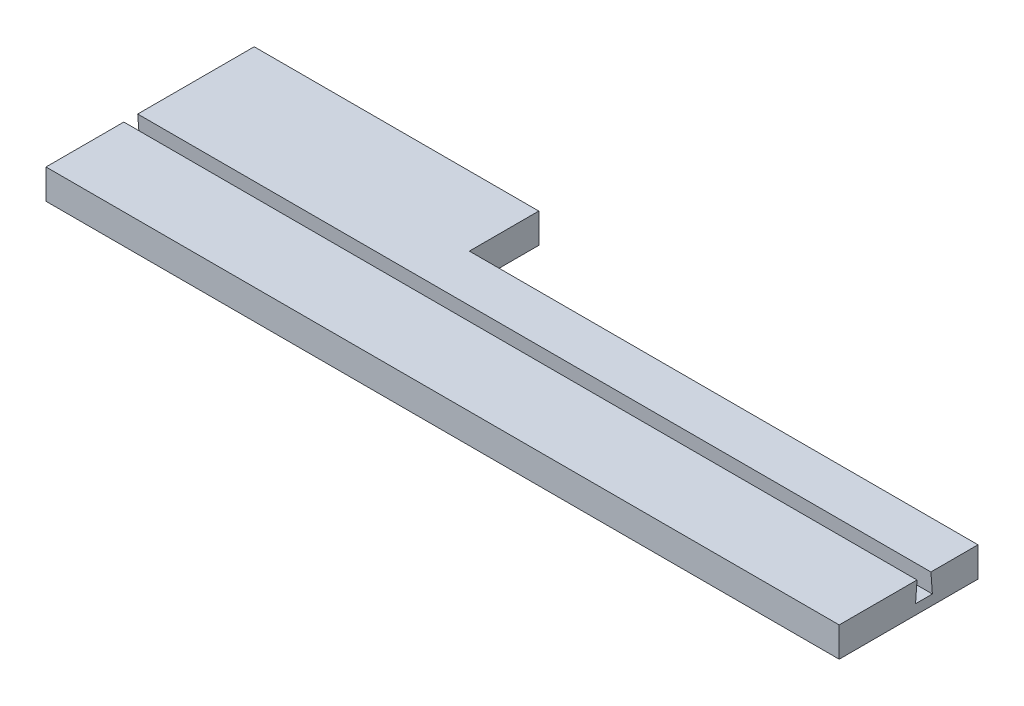
SolidWorks part; units mm, degrees
ref_plane "Front Plane" through (0, 0, 0) normal (0, 0, 1) x (1, 0, 0)
ref_plane "Top Plane" through (0, 0, 0) normal (0, 1, 0) x (1, 0, 0)
ref_plane "Right Plane" through (0, 0, 0) normal (1, 0, 0) x (0, 0, -1)
sketch "Sketch1" plane through (0, 0, 0) normal (0, 1, 0) x (1, 0, 0)
  line L1 (-7.5455, 9.1364) -> (72.4545, 9.1364)
  line L2 (-7.5455, 9.1364) -> (-7.5455, -4.8636)
  line L3 (-7.5455, -4.8636) -> (72.4545, -4.8636)
  line L4 (72.4545, 9.1364) -> (72.4545, -4.8636)
  dimension "D1" = 14
  dimension "D2" = 80
extrude "Boss-Extrude1" add sketch "Sketch1" along normal blind 2
sketch "Sketch2" plane through (0, 2, 0) normal (0, 1, 0) x (1, 0, 0)
  line L0 (72.4545, -4.8636) -> (72.4545, 9.1364) construction
  line L1 (-7.5455, -4.8636) -> (72.4545, -4.8636)
  line L2 (-7.5455, -4.8636) -> (-7.5455, 2.8364)
  line L3 (-7.5455, 2.8364) -> (72.4545, 2.8364)
  line L4 (72.4545, -4.8636) -> (72.4545, 2.8364)
  line L7 (-7.5455, 9.1364) -> (72.4545, 9.1364)
  line L8 (-7.5455, 9.1364) -> (-7.5455, 4.5364)
  line L9 (-7.5455, 4.5364) -> (72.4545, 4.5364)
  line L10 (72.4545, 9.1364) -> (72.4545, 4.5364)
  dimension "D1" = 7.7
  dimension "D2" = 1.7
  dimension "D3" = 4.6
extrude "Boss-Extrude2" add sketch "Sketch2" along normal blind 2 contours L3 L4 L1 L2 | L8 L9 L10 L7
sketch "Sketch3" plane through (0, 0, 0) normal (0, -1, 0) x (1, 0, 0)
  line L0 (72.4545, 4.8636) -> (72.4545, -9.1364) construction
  line L1 (-7.5455, -9.1364) -> (21.1545, -9.1364)
  line L2 (-7.5455, -9.1364) -> (-7.5455, -16.1364)
  line L3 (-7.5455, -16.1364) -> (21.1545, -16.1364)
  line L4 (21.1545, -9.1364) -> (21.1545, -16.1364)
  dimension "D1" = 7
  dimension "D2" = 51.3
extrude "Boss-Extrude3" add sketch "Sketch3" against normal up to surface (4 mm away) up to face at (32.4545, 4, -6.8364)
sketch "Sketch4" plane through (-7.5455, 0, 0) normal (-1, 0, 0) x (0, 0, 1)
  line L0 (-4.5364, 4) -> (-2.8364, 4) construction
  line L1 (-2.8364, 2) -> (-2.9864, 4)
  line L2 (-2.9864, 4) -> (-2.8364, 4)
  line L3 (-2.8364, 4) -> (-2.8364, 2)
  line L4 (-4.5364, 2) -> (-4.5364, 4)
  line L5 (-4.5364, 4) -> (-4.3864, 4)
  line L6 (-4.3864, 4) -> (-4.5364, 2)
  dimension "D1" = 0.15
  dimension "D2" = 0.15
extrude "Boss-Extrude4" add sketch "Sketch4" against normal up to surface (80 mm away) up to face at (72.4545, 2.5, -2.9114)
sketch "Sketch5" plane through (0, 0, 0) normal (0, -1, 0) x (1, 0, 0)
  line L0 (-7.5455, 4.8636) -> (72.4545, 4.8636)
  line L1 (72.4545, 4.8636) -> (72.4545, -9.1364)
  line L2 (72.4545, -9.1364) -> (21.1545, -9.1364)
  line L3 (21.1545, -9.1364) -> (21.1545, -16.1364)
  line L4 (21.1545, -16.1364) -> (-7.5455, -16.1364)
  line L5 (-7.5455, -16.1364) -> (-7.5455, 4.8636)
extrude "Cut-Extrude1" cut sketch "Sketch5" against normal blind 1
